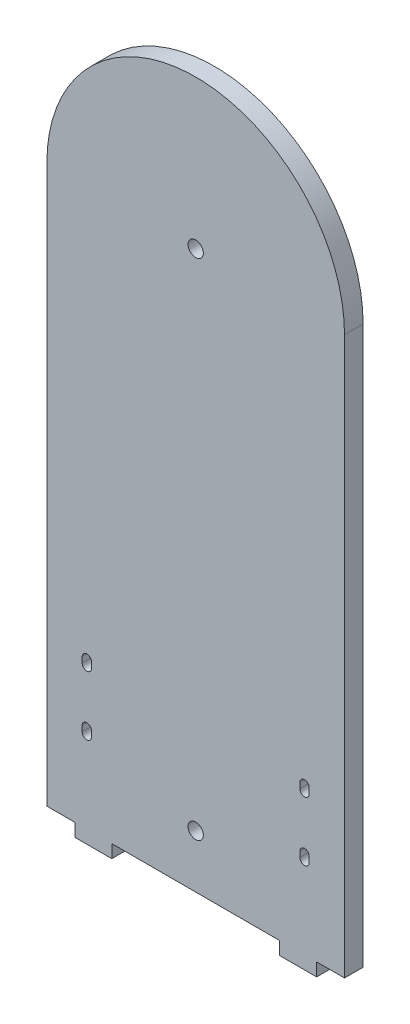
SolidWorks part; units mm, degrees
ref_plane "前基準面" through (0, 0, 0) normal (0, 0, 1) x (1, 0, 0)
ref_plane "上基準面" through (0, 0, 0) normal (0, 1, 0) x (1, 0, 0)
ref_plane "右基準面" through (0, 0, 0) normal (1, 0, 0) x (0, 0, -1)
sketch "草圖1" plane through (0, 0, 0) normal (0, 0, 1) x (1, 0, 0)
  line L0 (-80, 0) -> (-65, 0)
  line L1 (-80, 0) -> (-80, 299.5)
  line L2 (80, 0) -> (80, 299.5)
  line L3 (0, 299.9843) -> (0, -20.7711) construction
  line L5 (-65, 0) -> (-65, -7)
  line L6 (-65, -7) -> (-45.1, -7)
  line L7 (-45.1, 0) -> (-45.1, -7)
  line L12 (65, -7) -> (45.1, -7)
  line L13 (45.1, 0) -> (45.1, -7)
  line L15 (65, 0) -> (65, -7)
  line L16 (-45.1, 0) -> (45.1, 0)
  line L17 (65, 0) -> (80, 0)
  line L18 (-21.8, 299.5) -> (-15, 28.5) construction
  line L19 (28.5, 0) -> (-28.5, 0) construction
  line L20 (28.5, 0) -> (28.5, 57) construction
  line L21 (28.5, 57) -> (-28.5, 57) construction
  line L22 (-28.5, 0) -> (-28.5, 57) construction
  line L23 (21.8, 299.5) -> (15, 28.5) construction
  line L24 (-58.525, 76.1) -> (-58.525, 79.1) construction
  line L25 (-61.025, 76.1) -> (-61.025, 79.1)
  line L26 (-56.025, 76.1) -> (-56.025, 79.1)
  line L27 (-58.525, 44.1) -> (-58.525, 47.1) construction
  line L28 (-61.025, 44.1) -> (-61.025, 47.1)
  line L29 (-56.025, 44.1) -> (-56.025, 47.1)
  line L30 (-67.625, 89.2) -> (-67.625, 34) construction
  line L31 (-67.625, 89.2) -> (-49.425, 89.2) construction
  line L32 (-49.425, 89.2) -> (-49.425, 34) construction
  line L33 (-67.625, 34) -> (-49.425, 34) construction
  line L34 (-49.425, 61.6) -> (-67.625, 61.6) construction
  line L35 (-58.525, 89.2) -> (-58.525, 34) construction
  line L36 (58.525, 44.1) -> (58.525, 47.1) construction
  line L37 (61.025, 44.1) -> (61.025, 47.1)
  line L38 (56.025, 44.1) -> (56.025, 47.1)
  line L39 (58.525, 76.1) -> (58.525, 79.1) construction
  line L40 (61.025, 76.1) -> (61.025, 79.1)
  line L41 (56.025, 76.1) -> (56.025, 79.1)
  arc A0 (-80, 299.5) -> (80, 299.5) centre (0, 299.5) cw
  circle A1 centre (0, 299.5) radius 4.1
  circle A2 centre (0, 28.5) radius 4.1
  circle A3 centre (0, 28.5) radius 15 construction
  circle A4 centre (0, 299.5) radius 21.8 construction
  arc A5 (-61.025, 76.1) -> (-56.025, 76.1) centre (-58.525, 76.1) ccw
  arc A6 (-56.025, 79.1) -> (-61.025, 79.1) centre (-58.525, 79.1) ccw
  arc A7 (-61.025, 44.1) -> (-56.025, 44.1) centre (-58.525, 44.1) ccw
  arc A8 (-56.025, 47.1) -> (-61.025, 47.1) centre (-58.525, 47.1) ccw
  arc A9 (61.025, 44.1) -> (56.025, 44.1) centre (58.525, 44.1) cw
  arc A10 (56.025, 47.1) -> (61.025, 47.1) centre (58.525, 47.1) cw
  arc A11 (61.025, 76.1) -> (56.025, 76.1) centre (58.525, 76.1) cw
  arc A12 (56.025, 79.1) -> (61.025, 79.1) centre (58.525, 79.1) cw
  point P17 (0, 57)
  point P25 (-28.5, 28.5)
  point P31 (-58.525, 77.6)
  point P39 (-58.525, 45.6)
  point P45 (-58.525, 49.6)
  point P46 (-58.525, 73.6)
  point P47 (-58.525, 41.6)
  point P48 (-58.525, 81.6)
  point P49 (-58.525, 61.6)
  point P58 (-61.7656, 87.1975)
  point P59 (-56.9435, 39.3395)
  point P60 (0, 0)
  point P63 (58.525, 45.6)
  point P70 (58.525, 77.6)
  point P75 (-52.9586, 25.6951)
  point P76 (-56.9462, 24.8193)
  point P77 (-56.9474, 24.0745)
  point P78 (0, 379.5)
  dimension "D2" = 8.2
  dimension "D8" = 8.2
  dimension "D9" = 43.6
  dimension "D11" = 30
  dimension "D1" = 160
  dimension "D3" = 7
  dimension "D4" = 19.9
  dimension "D5" = 15
  dimension "D6" = 57
  dimension "D7" = 57
  dimension "D10" = 271
  dimension "D12" = 24
  dimension "D13" = 40
  dimension "D14" = 5
  dimension "D15" = 7.6
  dimension "D16" = 18.2
  dimension "D17" = 34
  dimension "D18" = 5.25
  dimension "D19" = 386.5
extrude "填料-伸長1" add sketch "草圖1" against normal blind 10
